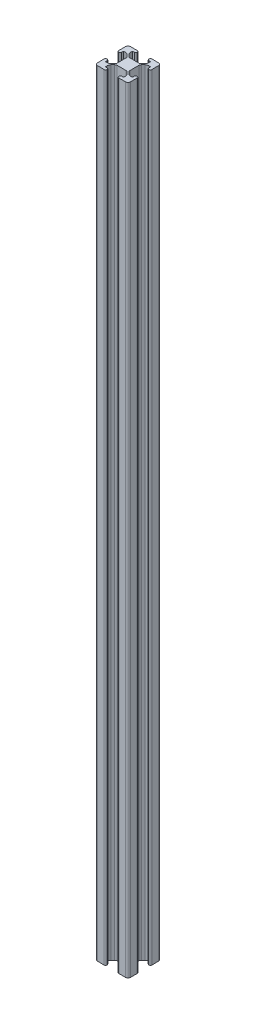
SolidWorks part; units mm, degrees
ref_plane "Front" through (0, 0, 0) normal (0, 0, 1) x (1, 0, 0)
ref_plane "Top" through (0, 0, 0) normal (0, 1, 0) x (1, 0, 0)
ref_plane "Right" through (0, 0, 0) normal (1, 0, 0) x (0, 0, -1)
sketch "Sketch2" plane through (0, 0, 0) normal (0, 1, 0) x (1, 0, 0)
  line L0 (-5.4, 4.8697) -> (-4.3393, 3.809)
  line L1 (-8.5, 10) -> (-4.4, 10)
  line L3 (-8.5, -10) -> (-4.4, -10)
  line L4 (10, 8.5) -> (10, 4.4)
  line L5 (-10, 10) -> (-9.5607, 9.5607) construction
  line L6 (-10, -10) -> (-9.5607, -9.5607) construction
  line L7 (-2.7483, 3.9) -> (2.7483, 3.9)
  line L8 (-3.9, 2.7483) -> (-3.9, -2.7483)
  line L9 (-2.7483, -3.9) -> (2.7483, -3.9)
  line L10 (3.9, 2.7483) -> (3.9, -2.7483)
  line L11 (-5.5, -8.2) -> (-4.4, -8.2)
  line L12 (-3.6, -9.2) -> (-3.6, -9)
  line L13 (-4.8697, 5.4) -> (-3.809, 4.3393)
  line L14 (4.8697, 5.4) -> (3.809, 4.3393)
  line L15 (5.4, 4.8697) -> (4.3393, 3.809)
  line L16 (-5.5, -8.2) -> (-5.5, -7.2)
  line L17 (9.5607, -9.5607) -> (10, -10) construction
  line L18 (-3.809, -4.3393) -> (-4.8697, -5.4)
  line L19 (-4.3393, -3.809) -> (-5.4, -4.8697)
  line L20 (3.809, -4.3393) -> (4.8697, -5.4)
  line L21 (4.3393, -3.809) -> (5.4, -4.8697)
  line L22 (9.5607, 9.5607) -> (10, 10) construction
  line L23 (8.5, -10) -> (4.4, -10)
  line L24 (3.6, -9.2) -> (3.6, -9)
  line L25 (5.5, -8.2) -> (4.4, -8.2)
  line L26 (0, 7.192) -> (0, -12.1556) construction
  line L27 (5.5, -8.2) -> (5.5, -7.2)
  line L28 (-8.2, 5.5) -> (-7.2, 5.5)
  line L29 (-8.2, 5.5) -> (-8.2, 4.4)
  line L30 (-10, 8.5) -> (-10, 4.4)
  line L31 (-8.2, -5.5) -> (-7.2, -5.5)
  line L32 (-10, -8.5) -> (-10, -4.4)
  line L33 (-8.2, -5.5) -> (-8.2, -4.4)
  line L34 (5.5, 8.2) -> (5.5, 7.2)
  line L35 (5.5, 8.2) -> (4.4, 8.2)
  line L36 (8.5, 10) -> (4.4, 10)
  line L37 (-5.5, 8.2) -> (-5.5, 7.2)
  line L38 (3.6, 9.2) -> (3.6, 9)
  line L39 (-5.5, 8.2) -> (-4.4, 8.2)
  line L40 (8.2, -5.5) -> (7.2, -5.5)
  line L41 (8.2, -5.5) -> (8.2, -4.4)
  line L42 (-3.6, 9.2) -> (-3.6, 9)
  line L43 (8.2, 5.5) -> (7.2, 5.5)
  line L44 (10, -4.4) -> (10, -8.5)
  line L45 (8.2, 5.5) -> (8.2, 4.4)
  line L46 (9, -3.6) -> (9.2, -3.6)
  line L47 (9, 3.6) -> (9.2, 3.6)
  line L48 (-9.2, 3.6) -> (-9, 3.6)
  line L49 (-9.2, -3.6) -> (-9, -3.6)
  line L52 (-8.5, 10) -> (-4.4, 10) [skipped]
  line L53 (10, -8.5) -> (10, -4.4) [skipped]
  line L54 (10, 8.5) -> (10, 4.4) [skipped]
  arc A0 (-10, -8.5) -> (-8.5, -10) centre (-8.5, -8.5) ccw
  arc A1 (8.5, -10) -> (10, -8.5) centre (8.5, -8.5) ccw
  arc A2 (8.5, 10) -> (10, 8.5) centre (8.5, 8.5) cw
  arc A3 (-8.5, 10) -> (-10, 8.5) centre (-8.5, 8.5) ccw
  arc A4 (-3.9, -2.7483) -> (-4.3393, -3.809) centre (-5.4, -2.7483) cw
  arc A5 (-2.7483, -3.9) -> (-3.809, -4.3393) centre (-2.7483, -5.4) ccw
  arc A6 (2.7483, -3.9) -> (3.809, -4.3393) centre (2.7483, -5.4) cw
  arc A7 (3.9, -2.7483) -> (4.3393, -3.809) centre (5.4, -2.7483) ccw
  arc A8 (3.9, 2.7483) -> (4.3393, 3.809) centre (5.4, 2.7483) cw
  arc A9 (2.7483, 3.9) -> (3.809, 4.3393) centre (2.7483, 5.4) ccw
  arc A10 (-2.7483, 3.9) -> (-3.809, 4.3393) centre (-2.7483, 5.4) cw
  arc A11 (-3.9, 2.7483) -> (-4.3393, 3.809) centre (-5.4, 2.7483) ccw
  arc A12 (-5.5, -7.2) -> (-4.8697, -5.4) centre (-2.6148, -7.2) cw
  arc A13 (-3.6, -9.2) -> (-4.4, -10) centre (-4.4, -9.2) cw
  arc A14 (-3.6, -9) -> (-4.4, -8.2) centre (-4.4, -9) ccw
  arc A15 (3.6, -9.2) -> (4.4, -10) centre (4.4, -9.2) ccw
  arc A16 (3.6, -9) -> (4.4, -8.2) centre (4.4, -9) cw
  arc A17 (5.5, -7.2) -> (4.8697, -5.4) centre (2.6148, -7.2) ccw
  arc A18 (-7.2, 5.5) -> (-5.4, 4.8697) centre (-7.2, 2.6148) cw
  arc A19 (-9, 3.6) -> (-8.2, 4.4) centre (-9, 4.4) ccw
  arc A20 (-9.2, 3.6) -> (-10, 4.4) centre (-9.2, 4.4) cw
  arc A21 (-7.2, -5.5) -> (-5.4, -4.8697) centre (-7.2, -2.6148) ccw
  arc A22 (-9, -3.6) -> (-8.2, -4.4) centre (-9, -4.4) cw
  arc A23 (-9.2, -3.6) -> (-10, -4.4) centre (-9.2, -4.4) ccw
  arc A24 (5.5, 7.2) -> (4.8697, 5.4) centre (2.6148, 7.2) cw
  arc A25 (3.6, 9) -> (4.4, 8.2) centre (4.4, 9) ccw
  arc A26 (3.6, 9.2) -> (4.4, 10) centre (4.4, 9.2) cw
  arc A27 (-5.5, 7.2) -> (-4.8697, 5.4) centre (-2.6148, 7.2) ccw
  arc A28 (-3.6, 9) -> (-4.4, 8.2) centre (-4.4, 9) cw
  arc A29 (-3.6, 9.2) -> (-4.4, 10) centre (-4.4, 9.2) ccw
  arc A30 (7.2, -5.5) -> (5.4, -4.8697) centre (7.2, -2.6148) cw
  arc A31 (9, -3.6) -> (8.2, -4.4) centre (9, -4.4) ccw
  arc A32 (9.2, -3.6) -> (10, -4.4) centre (9.2, -4.4) cw
  arc A33 (7.2, 5.5) -> (5.4, 4.8697) centre (7.2, 2.6148) ccw
  arc A34 (9, 3.6) -> (8.2, 4.4) centre (9, 4.4) cw
  arc A35 (9.2, 3.6) -> (10, 4.4) centre (9.2, 4.4) ccw
  point P0 (0, 0)
  point P6 (0, 0)
  point P41 (-3.9, -3.3697)
  point P44 (-3.3697, -3.9)
  point P47 (3.3697, -3.9)
  point P50 (3.9, -3.3697)
  dimension "D5" = 1.5
  dimension "D3" = 1.5
  dimension "D9" = 0.8
  dimension "D1" = 20
  dimension "D2" = 20
  dimension "D4" = 4
  dimension "D6" = 0.75
  dimension "D8" = 1.8
  dimension "D10" = 1
  dimension "D7" = 2
extrude "Boss-Extrude1" add sketch "Sketch2" along normal blind 470
